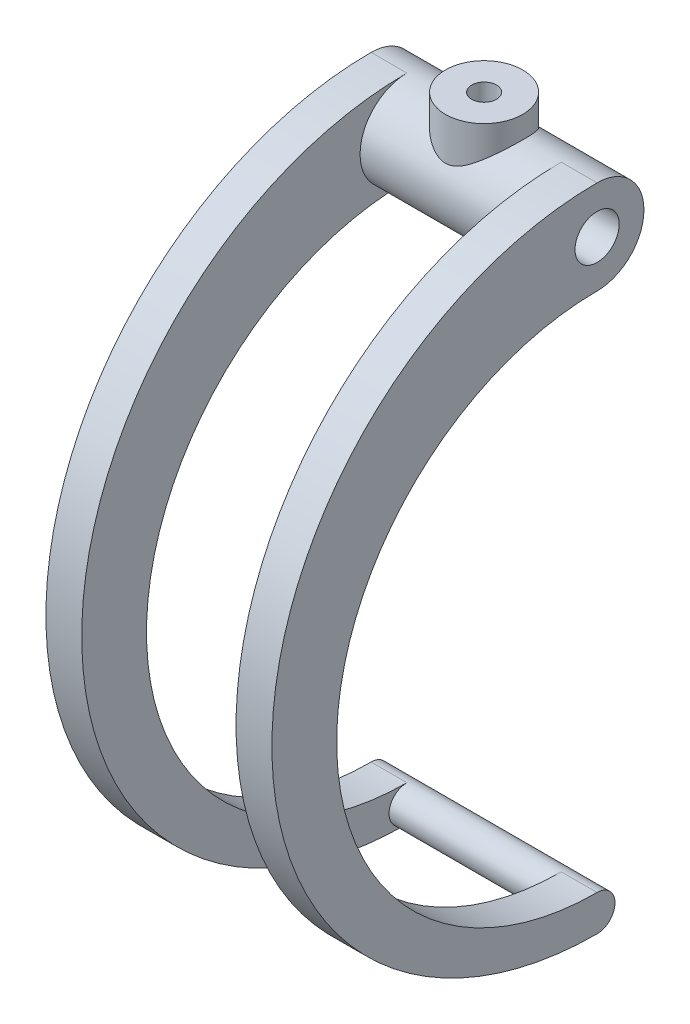
SolidWorks part; units mm, degrees
ref_plane "Front Plane" through (0, 0, 0) normal (0, 0, 1) x (1, 0, 0)
ref_plane "Top Plane" through (0, 0, 0) normal (0, 1, 0) x (1, 0, 0)
ref_plane "Right Plane" through (0, 0, 0) normal (1, 0, 0) x (0, 0, -1)
sketch "Sketch2" plane through (0, 0, 0) normal (1, 0, 0) x (0, 0, -1)
  circle A0 centre (0, 0) radius 13.4938
  circle A1 centre (0, 0) radius 6.3627
  dimension "D1" = 26.9875
  dimension "D2" = 12.7254
extrude "Boss-Extrude1" add sketch "Sketch2" along normal mid plane 65.0875
ref_plane "Plane1" through (0, 19.8438, 0) normal (0, 1, 0) x (1, 0, 0)
sketch "Sketch3" plane through (0, 19.8438, 0) normal (0, 1, 0) x (1, 0, 0)
  circle A0 centre (0, 0) radius 11.1125
  circle A1 centre (0, 0) radius 3.5719
  dimension "D1" = 22.225
  dimension "D2" = 7.1437
extrude "Boss-Extrude2" add sketch "Sketch3" against normal up to surface (12.1891 mm away) up to face at (32.5437, 0, -13.4938)
extrude "Cut-Extrude1" cut sketch "Sketch3<2>" against normal up to surface (14.5782 mm away) contours A1 region at (0, 19.8438, 0) up to face at (32.5437, 0, -6.3627)
sketch "Sketch3<2>" plane through (0, 19.8438, 0) normal (0, 1, 0) x (1, 0, 0) same geometry as "Sketch3"
sketch "Sketch4" plane through (32.5437, 0, 0) normal (1, 0, 0) x (0, 0, -1)
  arc A0 (0, 13.4938) -> (0, -173.8312) centre (0, -80.1688) ccw
  arc A1 (11.1125, 7.6546) -> (-11.1125, 7.6546) centre (0, 0) ccw construction
  circle A2 centre (0, 0) radius 6.3627 construction
  arc A3 (0, -13.4937) -> (0, -163.5125) centre (0, -88.5031) ccw
  circle A4 centre (0, -168.6719) radius 5.1594
  circle A5 centre (0, 0) radius 13.4938 construction
  arc A6 (0, -13.4937) -> (0, 13.4938) centre (0, 0) ccw
  circle A7 centre (0, 0) radius 6.3627
  circle M1 centre (0, 0) radius 13.4938
  circle M2 centre (0, 0) radius 6.3627
  dimension "D1" = 93.6625
  dimension "D2" = 10.3187
extrude "Boss-Extrude3" add sketch "Sketch4" against normal blind 10.3187 contours A4 A3 A0 M1 | M1 M2 | A4 region at (32.5437, 0, 15.5881) region at (32.5437, 9.2716, -9.2716) region at (32.5437, -168.6719, 0)
mirror "Mirror1" about plane through (0, 0, 0) normal (1, 0, 0) of "Boss-Extrude3"
extrude "Boss-Extrude4" add sketch "Sketch4<3>" against normal through all contours A4
sketch "Sketch4<3>" plane through (32.5437, 0, 0) normal (1, 0, 0) x (0, 0, -1) same geometry as "Sketch4"
equation "\"zg\"=1.46732"
